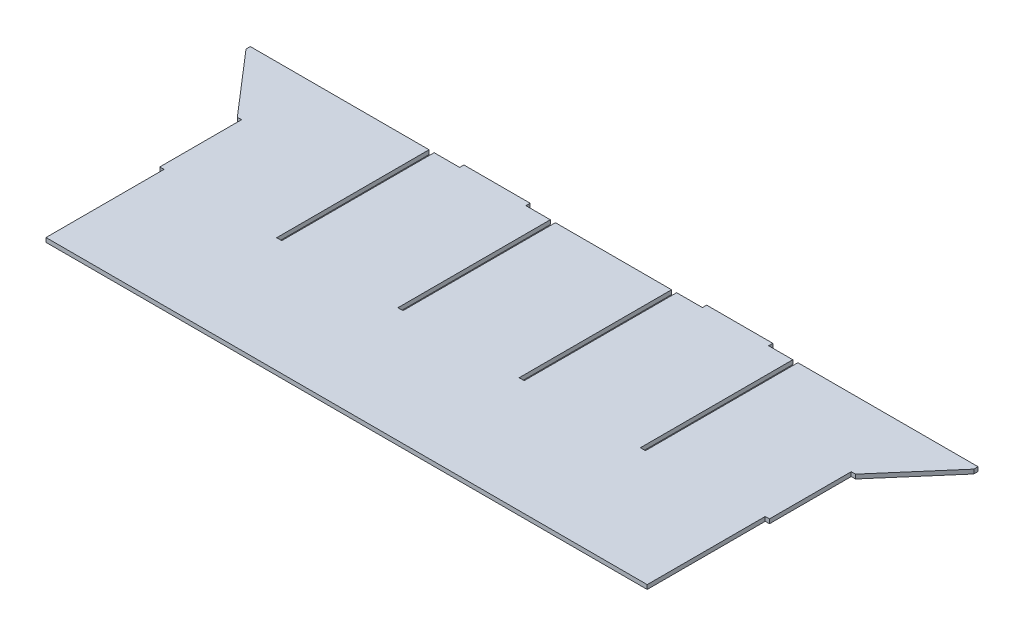
SolidWorks part; units mm, degrees
material "6061-T6 (SS)"
ref_plane "X-Y Datum" through (0, 0, 0) normal (0, 0, 1) x (1, 0, 0)
ref_plane "X-Z Datum" through (0, 0, 0) normal (0, 1, 0) x (1, 0, 0)
ref_plane "Y-Z Datum" through (0, 0, 0) normal (1, 0, 0) x (0, 0, -1)
sketch "Sketch1" plane through (0, 0, 0) normal (0, 0, 1) x (1, 0, 0)
  line L1 (-228.6115, -1.5875) -> (228.6115, -1.5875)
  line L2 (-228.6115, -1.5875) -> (-228.6115, 1.5875)
  line L3 (-228.6115, 1.5875) -> (228.6115, 1.5875)
  line L4 (228.6115, -1.5875) -> (228.6115, 1.5875)
  line L5 (-228.6115, -1.5875) -> (228.6115, 1.5875) construction
  line L6 (-228.6115, 1.5875) -> (228.6115, -1.5875) construction
  point P0 (0, 0)
  dimension "D1" = 3.175
  dimension "D2" = 457.223
extrude "Boss-Extrude1" add sketch "Sketch1" along normal blind 200.642
sketch "Sketch2" plane through (0, 1.5875, 0) normal (0, 1, 0) x (1, 0, 0)
  line L0 (228.6115, 0) -> (225.4365, 0)
  line L1 (228.6115, 0) -> (-228.6115, 0) construction
  line L2 (225.4365, 0) -> (137.8065, 0)
  line L3 (137.8065, 0) -> (133.986, 0)
  line L10 (133.986, 0) -> (137.8065, 0)
  line L11 (133.986, 0) -> (133.986, -114.3)
  line L12 (133.986, -114.3) -> (137.8065, -114.3)
  line L13 (137.8065, 0) -> (137.8065, -114.3)
  line M2 (228.6115, 0) -> (-228.6115, 0)
  dimension "D1" = 87.63
  dimension "D2" = 3.175
  dimension "D3" = 114.3
extrude "Cut-Extrude1" cut sketch "Sketch2" against normal through all contours L13 L11 L12 M2 region at (135.8963, 1.5875, 57.15)
pattern_linear "LPattern1" count 4 spacing 90.932 along (-1, 0, 0) of "Cut-Extrude1"
sketch "Sketch3" plane through (0, 0, 0) normal (0, 0, -1) x (-1, 0, 0)
  line L0 (-66.1907, -1.5583) -> (-66.1907, -1.5875)
  line L9 (-46.8745, -1.5875) -> (-133.986, -1.5875) construction
  line L11 (-133.986, 1.5875) -> (-46.8745, 1.5875) construction
  line L12 (47.878, 1.5875) -> (134.9895, 1.5875) construction
  line L13 (-66.1907, -1.5875) -> (-115.8495, -1.5875)
  line L14 (-66.1907, -1.5875) -> (-66.1907, 1.5875)
  line L15 (-66.1907, 1.5875) -> (-115.8495, 1.5875)
  line L16 (-115.8495, -1.5875) -> (-115.8495, 1.5875)
  line L17 (66.1907, -1.5875) -> (115.8495, -1.5875)
  line L18 (66.1907, -1.5875) -> (66.1907, 1.5875)
  line L19 (66.1907, 1.5875) -> (115.8495, 1.5875)
  line L20 (115.8495, -1.5875) -> (115.8495, 1.5875)
  line M4 (-46.8745, 1.5875) -> (-133.986, 1.5875)
  dimension "D2" = 49.6588
sketch "Sketch4" plane through (0, -1.5875, 0) normal (0, -1, 0) x (1, 0, 0)
  line L0 (-228.6115, 0) -> (-272.8865, 0)
  line L2 (-228.6115, 200.642) -> (-228.6115, 0) construction
  line L3 (-228.6115, 50.8) -> (-228.6115, 0)
  line L4 (-272.8865, 0) -> (-272.8865, 3.175)
  line L6 (-228.6115, 50.8) -> (-231.7865, 50.8)
  line L7 (-272.8865, 3.175) -> (-231.7865, 50.8)
  dimension "D1" = 44.275
  dimension "D2" = 50.8
  dimension "D3" = 3.175
extrude "Boss-Extrude3" add sketch "Sketch4" against normal blind 3.175
mirror "Mirror1" about plane through (0, 0, 0) normal (1, 0, 0) of "Boss-Extrude3"
sketch "Sketch5" plane through (0, -1.5875, 0) normal (0, -1, 0) x (1, 0, 0)
  line L1 (-228.6115, 200.642) -> (-225.4365, 200.642)
  line L2 (-228.6115, 200.642) -> (-228.6115, 112.128)
  line L3 (-228.6115, 112.128) -> (-225.4365, 112.128)
  line L4 (-225.4365, 200.642) -> (-225.4365, 112.128)
  dimension "D1" = 3.175
  dimension "D2" = 88.514
extrude "Cut-Extrude2" cut sketch "Sketch5" against normal blind 3.175
mirror "Mirror2" about plane through (0, 0, 0) normal (1, 0, 0) of "Cut-Extrude2"
extrude "Boss-Extrude4" add sketch "Sketch3" along normal blind 3.18 contours M4 | L17 region at (91.0201, 0, 0) region at (-91.0201, 0, 0)
